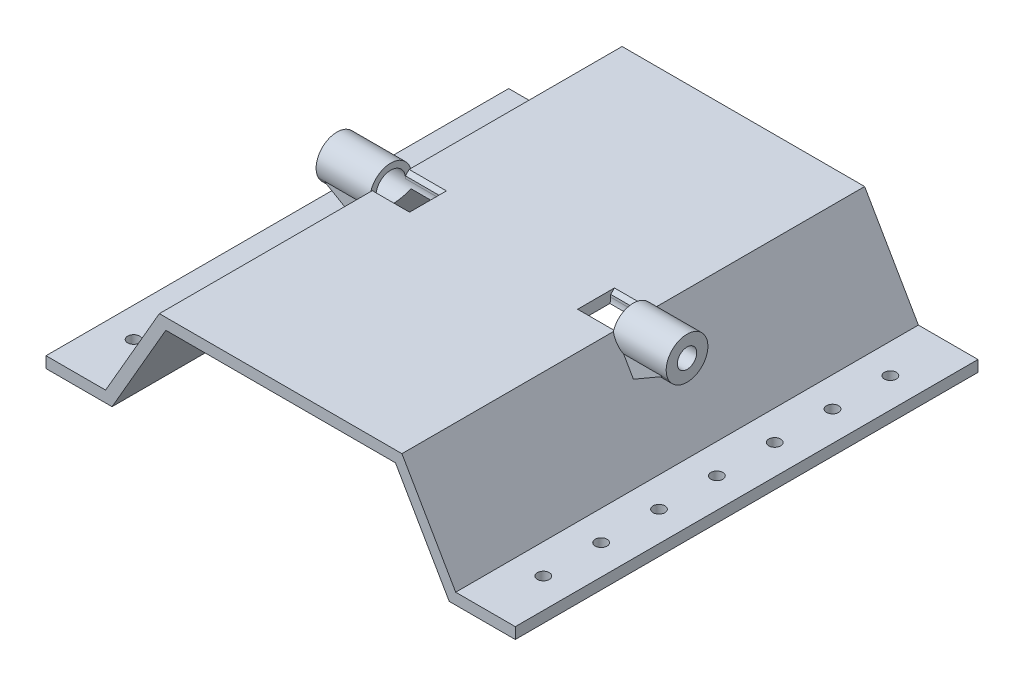
SolidWorks part; units mm, degrees
ref_plane "Спереди" through (0, 0, 0) normal (0, 0, 1) x (1, 0, 0)
ref_plane "Сверху" through (0, 0, 0) normal (0, 1, 0) x (1, 0, 0)
ref_plane "Справа" through (0, 0, 0) normal (1, 0, 0) x (0, 0, -1)
sketch "Эскиз1" plane through (0, 0, 0) normal (0, 0, 1) x (1, 0, 0)
  line L0 (-62.995, 0) -> (-45.2629, 0)
  line L1 (-45.2629, 0) -> (-30.8292, 25)
  line L2 (-30.8292, 25) -> (0, 25)
  line L3 (0, 25) -> (0, 28)
  line L4 (0, 28) -> (-32.5612, 28)
  line L5 (-32.5612, 28) -> (-46.995, 3)
  line L6 (-46.995, 3) -> (-62.995, 3)
  line L7 (-62.995, 3) -> (-62.995, 0)
  line L8 (-38.0461, 12.5) -> (-40.6441, 14) construction
  point P11 (0, 26.5)
  dimension "D1" = 16
  dimension "D2" = 3
  dimension "D3" = 25
  dimension "D4" = 120
  dimension "D5" = 62.995
extrude "Бобышка-Вытянуть1" add sketch "Эскиз1" along normal mid plane 124.23
sketch "Эскиз2" plane through (0, 0, 0) normal (1, 0, 0) x (0, 0, -1)
  line L0 (-5, 0) -> (5, 0)
  line L1 (-5, 0) -> (-5, 28)
  line L2 (-62.115, 28) -> (62.115, 28) construction
  line L3 (-5, 28) -> (5, 28)
  line L4 (5, 28) -> (5, 0)
  point P3 (0, 0)
  dimension "D1" = 10
extrude "Бобышка-Вытянуть2" add sketch "Эскиз2" against normal through all
sketch "Эскиз3" plane through (0, 0, 5) normal (0, 0, 1) x (1, 0, 0)
  line L0 (0, 25) -> (0, 0) construction
  line L1 (-45.2629, 0) -> (0, 0) construction
  line L2 (-45.2629, 0) -> (-30.8292, 25) construction
  line L3 (-30.8292, 25) -> (0, 25) construction
  line L4 (0, 25) -> (0, 0)
  line L5 (-45.2629, 0) -> (0, 0)
  line L6 (-45.2629, 0) -> (-30.8292, 25)
  line L7 (-30.8292, 25) -> (0, 25)
extrude "Вырез-Вытянуть1" cut sketch "Эскиз3" against normal blind 10
sketch "Эскиз4" plane through (0, 0, 0) normal (0, -1, 0) x (1, 0, 0)
  line L0 (-54.995, -62.115) -> (-54.995, 0) construction
  line L2 (-54.995, 0) -> (-62.995, 0) construction
  line L3 (-62.995, 62.115) -> (-62.995, -62.115) construction
  line L4 (-54.995, -62.115) -> (-54.995, -31.0575) construction
  line L5 (-54.995, -31.0575) -> (-54.995, 0) construction
  line L6 (-46.995, -62.115) -> (-62.995, -62.115) construction
  circle A0 centre (-54.995, 0) radius 1.6
  circle A1 centre (-54.995, -15.5287) radius 1.6
  circle A2 centre (-54.995, -31.0575) radius 1.6
  circle A3 centre (-54.995, -46.5862) radius 1.6
  circle A4 centre (-54.995, 46.5862) radius 1.6
  circle A5 centre (-54.995, 31.0575) radius 1.6
  circle A6 centre (-54.995, 15.5287) radius 1.6
  point P2 (0, 0)
  point P4 (-54.995, -31.0575)
  point P8 (-54.995, -15.5287)
  point P10 (-54.995, -46.5862)
  dimension "D1" = 3.2
extrude "Вырез-Вытянуть2" cut sketch "Эскиз4" against normal blind 3
sketch "Эскиз5" plane through (0, 0, -5) normal (0, 0, -1) x (-1, 0, 0)
  line L0 (62.995, 3) -> (62.995, 26.35) construction
  line L1 (62.995, 3) -> (62.995, 28) construction
  line L2 (62.995, 26.35) -> (33.5139, 26.35) construction
  line L3 (32.5612, 28) -> (46.995, 3) construction
  line L4 (46.995, 3) -> (62.995, 3) construction
  line L5 (46.995, 3) -> (62.995, 3)
  line L6 (62.995, 3) -> (62.995, 28)
  line L7 (46.995, 24.7) -> (46.995, 28)
  line L8 (62.995, 28) -> (32.5612, 28) construction
  line L9 (46.995, 28) -> (62.995, 28)
  line L10 (46.995, 24.7) -> (37.5986, 19.275)
  line L11 (37.5986, 19.275) -> (46.995, 3)
  line L12 (46.995, 3) -> (32.5612, 28) construction
  point P15 (46.995, 26.35)
  dimension "D1" = 23.35
extrude "Вырез-Вытянуть3" cut sketch "Эскиз5" against normal blind 10
sketch "Эскиз6" plane through (-46.995, 0, 0) normal (-1, 0, 0) x (0, 0, 1)
  line L0 (0, 24.7) -> (0, 28) construction
  line L1 (5, 24.7) -> (-5, 24.7) construction
  line L2 (5, 28) -> (-5, 28) construction
  circle A0 centre (0, 26.35) radius 2.6
  circle A1 centre (0, 26.35) radius 5.6
  line M2 (-5, 24.7) -> (5, 24.7)
  line M4 (5, 28) -> (-5, 28)
  dimension "D1" = 5.2
  dimension "D2" = 3
extrude "Бобышка-Вытянуть3" add sketch "Эскиз6" against normal up to vertex (14.4338 mm away) up to point (-32.5612, 28, -5)
extrude "Вырез-Вытянуть4" cut sketch "Эскиз6<2>" against normal blind 20 contours A0 M4 | L0 A0 M2 M4 | L0 A0 M2 M4 | A0 M2 region at (-46.995, 26.35, -1.2127) region at (-46.995, 24.3133, 0) region at (-46.995, 26.35, 1.2127) region at (-46.995, 28.3867, 0)
sketch "Эскиз6<2>" plane through (-46.995, 0, 0) normal (-1, 0, 0) x (0, 0, 1) same geometry as "Эскиз6"
sketch "Эскиз7" plane through (-32.5612, 0, 0) normal (1, 0, 0) x (0, 0, -1)
  circle A0 centre (0, 26.35) radius 3.95
  dimension "D1" = 7.9
extrude "Вырез-Вытянуть5" cut sketch "Эскиз7" against normal blind 8 and the other way blind 10
sketch "Эскиз8" plane through (-22.5612, 0, 0) normal (-1, 0, 0) x (0, 0, 1)
  line L0 (-3.95, 26.35) -> (-3.95, 28)
  line L1 (-3.95, 28) -> (3.95, 28)
  line L2 (3.95, 28) -> (3.95, 26.35)
  line L3 (-3.7121, 25) -> (3.7121, 25)
  line L4 (-3.5889, 28) -> (3.5889, 28) construction
  arc A0 (-3.5889, 28) -> (-3.7121, 25) centre (0, 26.35) ccw construction
  arc A1 (-3.95, 26.35) -> (-3.7121, 25) centre (0, 26.35) ccw
  arc A2 (3.7121, 25) -> (3.5889, 28) centre (0, 26.35) ccw construction
  arc A3 (3.7121, 25) -> (3.95, 26.35) centre (0, 26.35) ccw
extrude "Вырез-Вытянуть6" cut sketch "Эскиз8" along normal blind 10
chamfer "Фаска1" distance 1 angle 45 2 edges at (-27.5612, 28, 3.95) (-27.5612, 28, -3.95)
extrude "Вырез-Вытянуть7" cut sketch "Эскиз3<2>" against normal blind 10
sketch "Эскиз3<2>" plane through (0, 0, 5) normal (0, 0, 1) x (1, 0, 0) same geometry as "Эскиз3"
sketch "Эскиз9" plane through (0, 0, 62.115) normal (0, 0, 1) x (1, 0, 0)
  line L0 (-45.2629, 6) -> (-45.2629, 31.95)
  line L1 (-32.5612, 28) -> (-46.995, 3) construction
  line L2 (-32.5612, 31.95) -> (-46.995, 31.95) construction
  line L3 (-45.2629, 31.95) -> (-62.995, 31.95)
  line L4 (-62.995, 31.95) -> (-62.995, 3)
  line L5 (-62.995, 3) -> (-46.995, 3)
  line L6 (-46.995, 3) -> (-45.2629, 6)
  point P6 (0, 0)
extrude "Вырез-Вытянуть8" cut sketch "Эскиз9" against normal through all
sketch "Эскиз10" plane through (-45.2629, 0, 0) normal (-1, 0, 0) x (0, 0, 1)
  line L0 (-5, 23.8281) -> (-4.9333, 23.7)
  line L1 (5, 23.8281) -> (4.9333, 23.7)
  arc A0 (-4.9333, 23.7) -> (4.9333, 23.7) centre (0, 26.35) ccw construction
  circle A1 centre (0, 26.35) radius 2.6
  circle A2 centre (0, 26.35) radius 2.6
  arc A3 (5, 23.8281) -> (-5, 23.8281) centre (0, 26.35) ccw construction
  arc A4 (-4.9333, 23.7) -> (4.9333, 23.7) centre (0, 26.35) ccw
  arc A5 (5, 23.8281) -> (-5, 23.8281) centre (0, 26.35) ccw
  dimension "D1" = 0
extrude "Бобышка-Вытянуть4" add sketch "Эскиз10" along normal blind 1.73
mirror "Зеркальное отражение1" about plane through (0, 25, 62.115) normal (-1, 0, 0) of bodies 114
